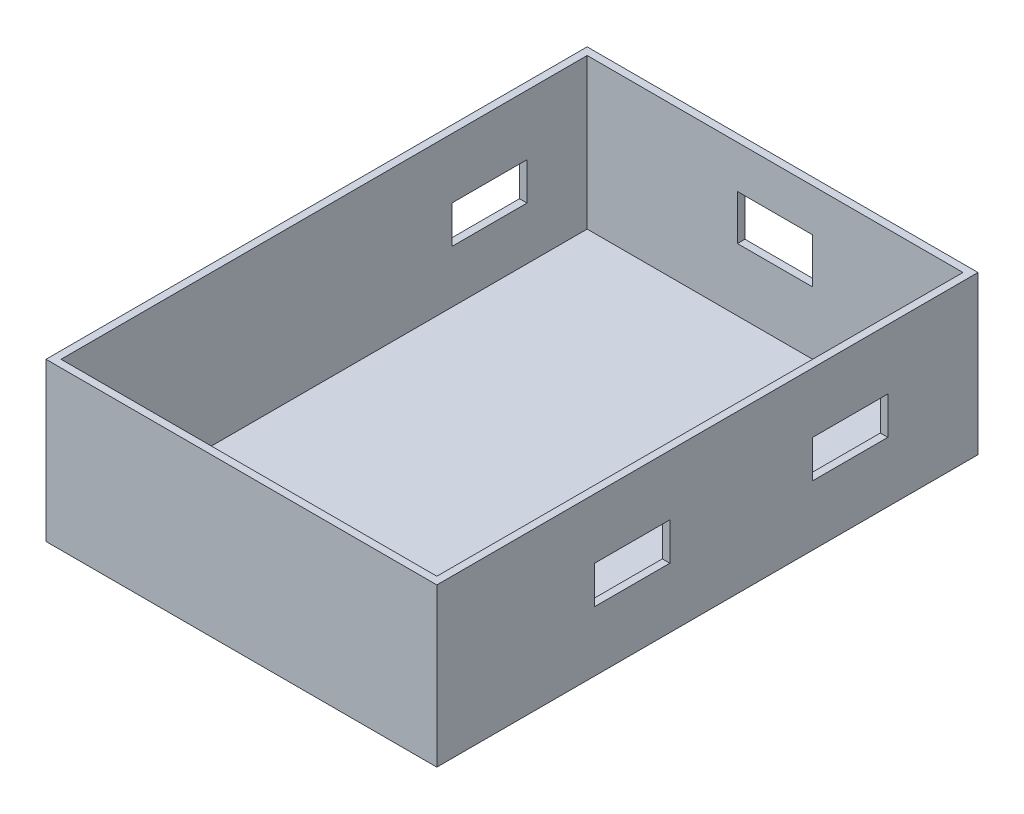
SolidWorks part; units mm, degrees
ref_plane "Alzado" through (0, 0, 0) normal (0, 0, 1) x (1, 0, 0)
ref_plane "Planta" through (0, 0, 0) normal (0, 1, 0) x (1, 0, 0)
ref_plane "Vista lateral" through (0, 0, 0) normal (1, 0, 0) x (0, 0, -1)
sketch "Croquis1" plane through (0, 0, 0) normal (0, 1, 0) x (1, 0, 0)
  line L0 (-1, -1) -> (51, -1)
  line L1 (0, 0) -> (50, 0)
  line L2 (0, 0) -> (0, 70)
  line L3 (0, 70) -> (50, 70)
  line L4 (50, 0) -> (50, 70)
  line L5 (51, -1) -> (51, 71)
  line L6 (-1, 71) -> (51, 71)
  line L7 (-1, -1) -> (-1, 71)
  dimension "D1" = 70
  dimension "D2" = 50
  dimension "D3" = 1
extrude "Saliente-Extruir1" add sketch "Croquis1" along normal blind 1 contours L2 L1 L4 L3
extrude "Saliente-Extruir2" add sketch "Croquis1<3>" along normal blind 21
sketch "Croquis1<3>" plane through (0, 0, 0) normal (0, 1, 0) x (1, 0, 0) same geometry as "Croquis1"
sketch "Croquis3" plane through (0, 0, -71) normal (0, 0, -1) x (-1, 0, 0)
  line L0 (-25, 21) -> (-25, 0)
  line L1 (-51, 21) -> (1, 21) construction
  line L2 (-51, 0) -> (1, 0) construction
  line L4 (-30, 15.33) -> (-20, 15.33)
  line L5 (-30, 15.33) -> (-30, 9.33)
  line L6 (-30, 9.33) -> (-20, 9.33)
  line L7 (-20, 15.33) -> (-20, 9.33)
  line L8 (-30, 15.33) -> (-20, 9.33) construction
  line L9 (-30, 9.33) -> (-20, 15.33) construction
  point P6 (-25, 12.33)
  dimension "D1" = 6
  dimension "D2" = 10
  dimension "D3" = 12.33
extrude "Cortar-Extruir1" cut sketch "Croquis3" against normal blind 21 contours L5 L6 L0 L4 | L7 L4 L0 L6 region at (22.5, 12.33, -71) region at (27.5, 12.33, -71)
sketch "Croquis4" plane through (51, 0, 0) normal (1, 0, 0) x (0, 0, -1)
  line L0 (-1, 0) -> (71, 0) construction
  line L3 (-1, 10.5) -> (71, 10.5)
  line L4 (-1, 21) -> (-1, 0) construction
  line L5 (71, 21) -> (71, 0) construction
  line L7 (49, 8) -> (59, 8)
  line L8 (49, 8) -> (49, 13)
  line L9 (49, 13) -> (59, 13)
  line L10 (59, 8) -> (59, 13)
  line L11 (49, 8) -> (59, 13) construction
  line L12 (49, 13) -> (59, 8) construction
  line L13 (20, 8) -> (30, 8)
  line L14 (20, 8) -> (20, 13)
  line L15 (20, 13) -> (30, 13)
  line L16 (30, 8) -> (30, 13)
  line L17 (20, 8) -> (30, 13) construction
  line L18 (20, 13) -> (30, 8) construction
  point P2 (25, 10.5)
  point P12 (54, 10.5)
  dimension "D1" = 5
  dimension "D2" = 10
  dimension "D3" = 12
  dimension "D4" = 8
  dimension "D5" = 21
  dimension "D6" = 5
  dimension "D7" = 10
extrude "Cortar-Extruir3" cut sketch "Croquis4" against normal blind 29 contours L13 L16 L3 L14 | L3 L16 L15 L14 | L7 L10 L3 L8 | L3 L10 L9 L8 region at (51, 11.75, -25) region at (51, 9.25, -25) region at (51, 11.75, -54) region at (51, 9.25, -54)
sketch "Croquis5" plane through (-1, 0, 0) normal (-1, 0, 0) x (0, 0, 1)
  line L0 (-71, 10.5) -> (1, 10.5)
  line L1 (-71, 21) -> (-71, 0) construction
  line L2 (1, 21) -> (1, 0) construction
  line L4 (-62, 13) -> (-52, 13)
  line L5 (-62, 13) -> (-62, 8)
  line L6 (-62, 8) -> (-52, 8)
  line L7 (-52, 13) -> (-52, 8)
  line L8 (-62, 13) -> (-52, 8) construction
  line L9 (-62, 8) -> (-52, 13) construction
  point P6 (-57, 10.5)
  point P11 (-24, 10.5)
  dimension "D1" = 5
  dimension "D2" = 10
  dimension "D5" = 25
  dimension "D6" = 14
extrude "Cortar-Extruir4" cut sketch "Croquis5" against normal blind 29 contours L7 L4 L5 L0 | L5 L4 L7 L6 region at (-1, 11.75, -57)
